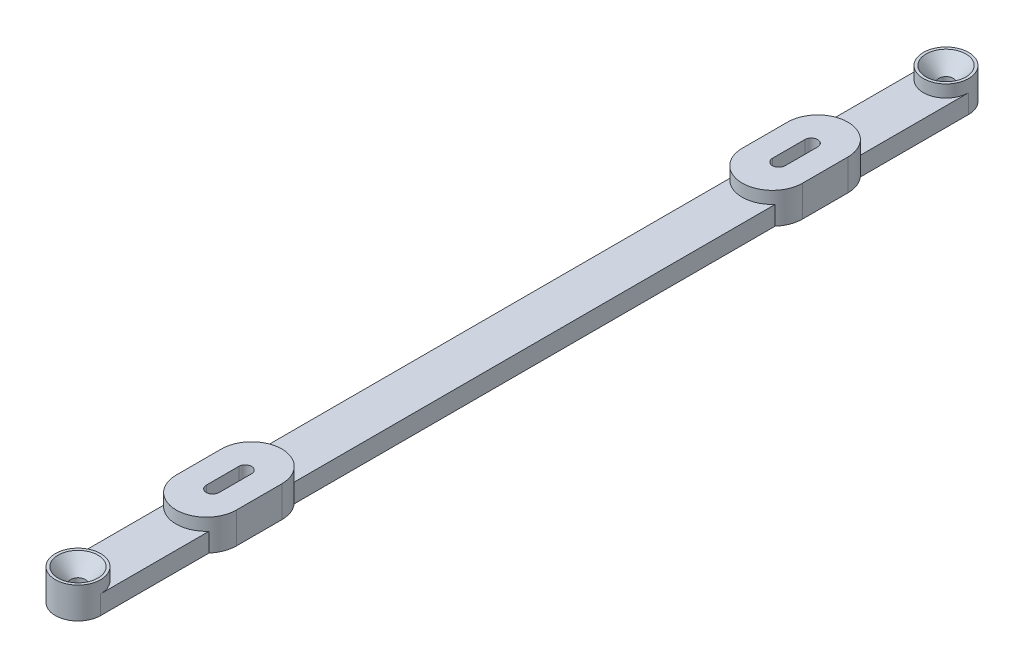
SolidWorks part; units mm, degrees
ref_plane "Front Plane" through (0, 0, 0) normal (0, 0, 1) x (1, 0, 0)
ref_plane "Top Plane" through (0, 0, 0) normal (0, 1, 0) x (1, 0, 0)
ref_plane "Right Plane" through (0, 0, 0) normal (1, 0, 0) x (0, 0, -1)
sketch "Arm Base Sketch" plane through (0, 0, 0) normal (0, 1, 0) x (1, 0, 0)
  line L0 (-6, 115) -> (6, 115)
  line L1 (6, 115) -> (6, 0)
  line L2 (6, 0) -> (-6, 0)
  line L3 (-6, 0) -> (-6, 115)
  point P2 (0, 0)
  dimension "D1" = 115
  dimension "D2" = 12
extrude "Arm Base Extrude" add sketch "Arm Base Sketch" along normal blind 5
sketch "Screw Bases Sketch" plane through (0, 0, 0) normal (0, -1, 0) x (1, 0, 0)
  line L0 (6, -115) -> (-6, -115) construction
  line L1 (0, -81) -> (0, -69) construction
  line L2 (-8, -81) -> (-8, -69)
  line L3 (8, -81) -> (8, -69)
  circle A0 centre (0, -115) radius 6
  arc A1 (-8, -81) -> (8, -81) centre (0, -81) ccw
  arc A2 (8, -69) -> (-8, -69) centre (0, -69) ccw
  point P8 (0, -75)
  dimension "D1" = 16
  dimension "D2" = 12
  dimension "D3" = 75
extrude "Screw Bases Extrude" add sketch "Screw Bases Sketch" against normal blind 8.25
hole_wizard "Power Supply Mounting Slot" positions "Power Supply Mounting Slot Position Sketch" profile "Power Supply Mounting Slot Profile Sketch" size "M3" standard "ANSI Metric" slot yes end condition through all
sketch "Power Supply Mounting Slot Position Sketch" plane through (0, 0, 0) normal (0, -1, 0) x (-1, 0, 0)
  line L0 (0, 81) -> (0, 69) construction
  line L1 (0, 81) -> (0, 69) construction
  point P0 (0, 75)
  point P5 (0, 0)
  point P7 (0, 0)
  point P10 (0, 79.1793)
  point P11 (0, 0)
sketch "Power Supply Mounting Slot Profile Sketch" plane through (0, 0, -75) normal (1, 0, 0) x (0, 0, -1)
  line L0 (0, 0) -> (0, 8.25)
  line L1 (0, 8.25) -> (1.7, 8.25)
  line L3 (1.7, 8.25) -> (1.7, 2.4)
  line L4 (1.7, 2.4) -> (3.5, 2.4)
  line L5 (3.5, 2.4) -> (3.5, 0)
  line L7 (3.5, 0) -> (0, 0)
  line L11 (0, -6.35) -> (0, 107.95) construction
  dimension "Thru Hole Dia." = 3.4
  dimension "Thru Hole Depth" = 8.25
  dimension "C'Bore Dia." = 7
  dimension "C'Bore Depth" = 2.4
hole_wizard "No. 6 Mounting Screws" positions "No. 6 Mounting Screws Position Sketch" profile "No. 6 Mounting Screws Profile Sketch" countersink size "#6" standard "ANSI Inch" end condition through all
sketch "No. 6 Mounting Screws Position Sketch" plane through (0, 8.25, 0) normal (0, 1, 0) x (1, 0, 0)
  circle A0 centre (0, 115) radius 6 construction
  point P0 (0, 115)
  point P3 (0, 0)
sketch "No. 6 Mounting Screws Profile Sketch" plane through (0, 8.25, -115) normal (1, 0, 0) x (0, 0, 1)
  line L0 (0, 0) -> (0, 8.25)
  line L1 (0, 8.25) -> (1.8986, 8.25)
  line L2 (1.8986, 8.25) -> (1.8986, 3.8919)
  line L3 (1.8986, 3.8919) -> (5.2819, 0)
  line L5 (5.2819, 0) -> (0, 0)
  line L6 (-1.8987, 3.8919) -> (-5.2819, 0) construction
  line L11 (0, -6.35) -> (0, 107.95) construction
  dimension "Thru Hole Dia." = 3.7973
  dimension "Thru Hole Depth" = 8.25
  dimension "Near C'Sink Dia." = 10.5637
  dimension "Near C'Sink Angle" = 82
mirror "Mirror" about plane through (6, 5, 0) normal (0, 0, -1) of bodies 104
